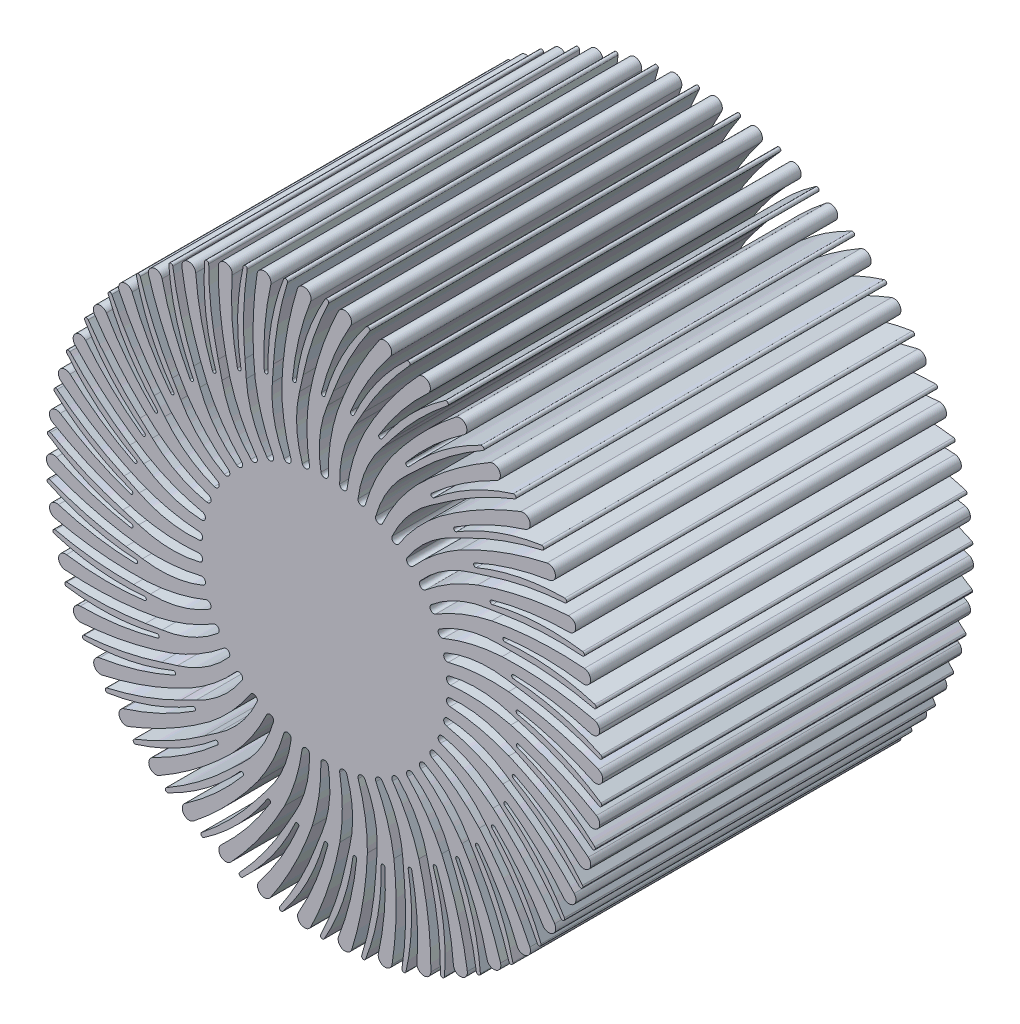
SolidWorks part; units mm, degrees
material "6061 Alaşım"
ref_plane "Ön Düzlem" through (0, 0, 0) normal (0, 0, 1) x (1, 0, 0)
ref_plane "Üst Düzlem" through (0, 0, 0) normal (0, 1, 0) x (1, 0, 0)
ref_plane "Sağ Düzlem" through (0, 0, 0) normal (1, 0, 0) x (0, 0, -1)
sketch "Çizim1" plane through (0, 0, 0) normal (0, 0, 1) x (1, 0, 0)
  circle A0 centre (0, 0) radius 30
  dimension "D1" = 60
extrude "Yükseklik-Ekstrüzyon1" add sketch "Çizim1" along normal blind 40
sketch "Çizim3" plane through (0, 0, 0) normal (0, 0, 1) x (1, 0, 0)
  line L0 (-12.0976, 17.1444) -> (-11.2032, 17.4576) construction
  arc A0 (-11.4791, 18.505) -> (-11.0701, 16.7523) centre (-79.4373, 1.7217) cw
  arc A1 (-12.0976, 17.1444) -> (-11.7201, 17.2766) centre (-11.9099, 17.2134) ccw
  arc A2 (-12.0976, 17.1444) -> (-13.9732, 26.5471) centre (17, 27.8369) cw
  circle A3 centre (0, 0) radius 30 construction
  arc A4 (-12.9278, 27.0716) -> (-11.7201, 17.2766) centre (12, 25.1732) ccw
  arc A5 (-13.9732, 26.5471) -> (-12.9278, 27.0716) centre (0, 0) cw
  arc A6 (-11.0701, 16.7523) -> (-7.9406, 10.9504) centre (0.65, 19.329) ccw
  arc A7 (-7.9406, 10.9504) -> (-7.3277, 11.4607) centre (-7.6543, 11.2297) ccw
  arc A8 (-12.498, 27.2727) -> (-11.4791, 18.505) centre (22.5, 26.8966) ccw
  arc A9 (-7.3277, 11.4607) -> (-10.1744, 17.3237) centre (9, 23.0108) cw
  arc A10 (-12.498, 27.2727) -> (-11.4619, 27.7241) centre (0, 0) cw
  arc A11 (-10.1744, 17.3237) -> (-11.4619, 27.7241) centre (26.0327, 27.0858) cw
  dimension "D1" = 0.2
  dimension "D2" = 31
  dimension "D3" = 25
  dimension "D6" = 0.4
  dimension "D7" = 12
  dimension "D9" = 35
  dimension "D11" = 70
  dimension "D12" = 20
  dimension "D14" = 37.5
  dimension "D4" = 12
  dimension "D5" = 17
  dimension "D8" = 0.65
  dimension "D10" = 22.5
  dimension "D13" = 9
  dimension "D15" = 26.0327
extrude "Kes-Ekstrüzyon3" cut sketch "Çizim3" against normal up to surface (40 mm away) contours A5 A4 A1 A2 | A10 A11 A9 A7 A6 A0 A8
pattern_circular "Dairesel Kaplama1" count 42 over 360 about axis through (0, 0, 0) along (0, 0, 1) of "Kes-Ekstrüzyon3"
fillet "Radyus1" radius 0.65 2 edges at (27.2593, -12.5272, 20) (26.4997, -14.0629, 20)
fillet "Radyus2" radius 0.2 2 edges at (27.8901, -11.0517, 20) (27.7118, -11.4915, 20)
sketch "Çizim4" plane through (0, 0, 40) normal (0, 0, 1) x (1, 0, 0)
  line L0 (-11.4671, 27.2172) -> (-11.7755, 28.0932)
  line L1 (-11.7755, 28.0932) -> (-9.2921, 28.6865)
  line L2 (-9.2921, 28.6865) -> (-9.965, 27.162)
  line L3 (-12.9372, 26.944) -> (-13.2877, 27.402)
  line L4 (-13.2877, 27.402) -> (-12.0631, 27.613)
  line L5 (-12.0631, 27.613) -> (-12.5, 26.9283)
  arc A0 (-11.4671, 27.2172) -> (-9.965, 27.162) centre (-10.7151, 27.2146) cw
  arc A3 (-11.4619, 27.7241) -> (-10.1744, 17.3237) centre (26.0327, 27.0858) ccw construction
  arc A4 (-9.8604, 28.3332) -> (-9.4072, 18.756) centre (20.959, 24.9923) ccw construction
  circle A5 centre (0, 0) radius 30 construction
  arc A6 (-12.9372, 26.944) -> (-12.5, 26.9283) centre (-12.7189, 26.9285) cw
  arc A7 (-12.9278, 27.0716) -> (-11.7201, 17.2766) centre (12, 25.1732) ccw construction
  arc A8 (-12.498, 27.2727) -> (-11.4791, 18.505) centre (22.5, 26.8966) ccw construction
extrude "Kes-Ekstrüzyon4" cut sketch "Çizim4" against normal blind 80
pattern_circular "Dairesel Kaplama7" count 42 over 360 about axis through (-0.0021, -0.004, 0) along (0, 0, 1) of "Kes-Ekstrüzyon4"
